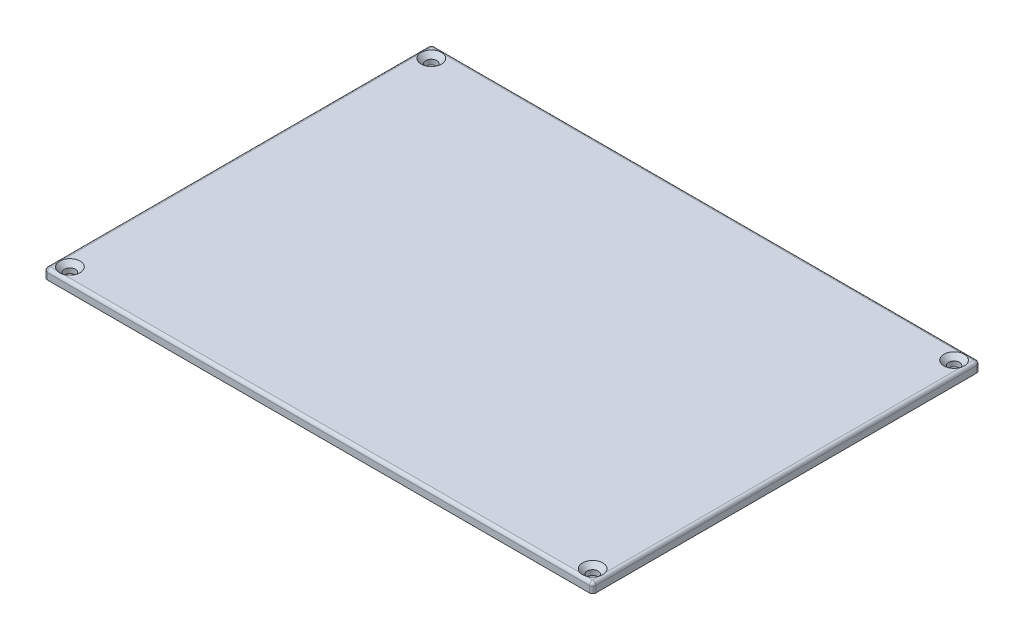
SolidWorks part; units mm, degrees
ref_plane "Front Plane" through (0, 0, 0) normal (0, 0, 1) x (1, 0, 0)
ref_plane "Top Plane" through (0, 0, 0) normal (0, 1, 0) x (1, 0, 0)
ref_plane "Right Plane" through (0, 0, 0) normal (1, 0, 0) x (0, 0, -1)
sketch "Sketch1" plane through (0, 0, 0) normal (0, 1, 0) x (1, 0, 0)
  line L1 (-155.5644, 40.1584) -> (14.4356, 40.1584)
  line L2 (-155.5644, 40.1584) -> (-155.5644, -79.8416)
  line L3 (-155.5644, -79.8416) -> (14.4356, -79.8416)
  line L4 (14.4356, 40.1584) -> (14.4356, -79.8416)
  dimension "D1" = 120
  dimension "D2" = 170
extrude "Boss-Extrude1" add sketch "Sketch1" along normal blind 3 contours L3 L4 L1 L2
sketch "Sketch2" plane through (0, 3, 0) normal (0, 1, 0) x (1, 0, 0)
  line L0 (-155.5644, 40.1584) -> (14.4356, 40.1584) construction
  line L1 (-155.5644, 40.1584) -> (-155.5644, -79.8416) construction
  line L2 (14.4356, 40.1584) -> (14.4356, -79.8416) construction
  line L3 (-155.5644, -79.8416) -> (14.4356, -79.8416) construction
  point P0 (10.4356, 36.1584)
  point P1 (-151.5644, 36.1584)
  point P2 (-151.5644, -75.8416)
  point P3 (10.4356, -75.8416)
  point P4 (10.4356, 36.1584)
  dimension "D1" = 4
  dimension "D2" = 4
  dimension "D3" = 4
  dimension "D4" = 4
hole_wizard "CSK for M3 Flat Head Machine Screw1" positions "Sketch3" profile "Sketch4" countersink size "M3" standard "ANSI Metric" end condition through all
sketch "Sketch3" plane through (0, 3, 0) normal (0, 1, 0) x (1, 0, 0)
  point P0 (-151.5644, 36.1584)
  point P3 (10.4356, 36.1584)
  point P6 (10.4356, -75.8416)
  point P9 (-151.5644, -75.8416)
sketch "Sketch4" plane through (-151.5644, 3, -36.1584) normal (1, 0, 0) x (0, 0, 1)
  line L0 (0, 0) -> (0, 3)
  line L1 (0, 3) -> (1.7, 3)
  line L2 (1.7, 3) -> (1.7, 1.45)
  line L3 (1.7, 1.45) -> (3.15, 0)
  line L5 (3.15, 0) -> (0, 0)
  line L6 (-1.7, 1.45) -> (-3.15, 0) construction
  line L11 (0, -6.35) -> (0, 107.95) construction
  dimension "Thru Hole Dia." = 3.4
  dimension "Thru Hole Depth" = 3
  dimension "Near C'Sink Dia." = 6.3
  dimension "Near C'Sink Angle" = 90
fillet "Fillet2" radius 1 8 edges at (-155.5644, 3, 19.8416) (-70.5644, 3, 79.8416) (14.4356, 3, 19.8416) (-155.5644, 1.5, -40.1584) (14.4356, 1.5, -40.1584) (14.4356, 1.5, 79.8416) (-155.5644, 1.5, 79.8416) (-70.5644, 3, -40.1584)
equation "\"D2@Sketch2\"=\"D1@Sketch2\""
equation "\"D3@Sketch2\"=\"D1@Sketch2\""
equation "\"D4@Sketch2\"=\"D1@Sketch2\""
